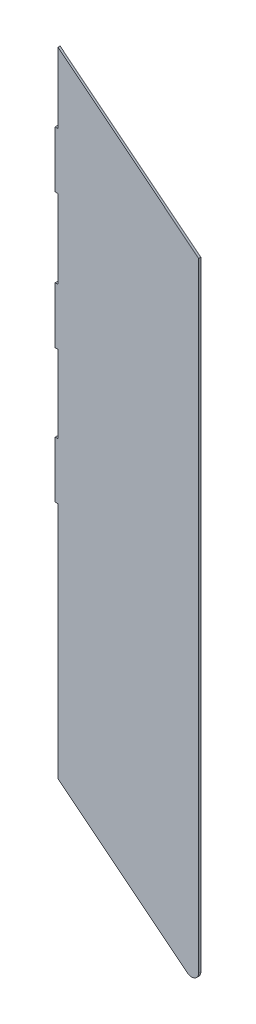
SolidWorks part; units mm, degrees
material "1345 Alloy"
ref_plane "Front Plane" through (0, 0, 0) normal (0, 0, 1) x (1, 0, 0)
ref_plane "Top Plane" through (0, 0, 0) normal (0, 1, 0) x (1, 0, 0)
ref_plane "Right Plane" through (0, 0, 0) normal (1, 0, 0) x (0, 0, -1)
sketch "Sketch1" plane through (0, 0, 0) normal (0, 0, 1) x (1, 0, 0)
  line L0 (0, -152.1368) -> (0, 297.8632)
  line L1 (0, 297.8632) -> (100, 217.8632)
  line L2 (100, 217.8632) -> (100, -232.1368)
  line L3 (0, -152.1368) -> (100, -232.1368)
  dimension "D1" = 100
  dimension "D2" = 80
extrude "Boss-Extrude1" add sketch "Sketch1" along normal blind 1.5
sketch "Sketch7" plane through (0, 0, 0) normal (-1, 0, 0) x (0, 0, 1)
  line L0 (0, 247.8632) -> (1.5, 247.8632)
  line L3 (1.5, 247.8632) -> (1.5, 207.8632)
  line L4 (1.5, 207.8632) -> (0, 207.8632)
  line L5 (0, 207.8632) -> (0, 247.8632)
  line L8 (0, 151.9834) -> (1.5, 151.9834)
  line L9 (0, 151.9834) -> (0, 111.9834)
  line L10 (0, 111.9834) -> (1.5, 111.9834)
  line L11 (1.5, 151.9834) -> (1.5, 111.9834)
  line L12 (0, 16.9834) -> (1.5, 16.9834)
  line L13 (0, 16.9834) -> (0, 56.9834)
  line L14 (0, 56.9834) -> (1.5, 56.9834)
  line L15 (1.5, 16.9834) -> (1.5, 56.9834)
  line L20 (1.5, 297.8632) -> (0, 297.8632) construction
  dimension "D1" = 40
  dimension "D2" = 50
  dimension "D3" = 40
  dimension "D4" = 40
  dimension "D6" = 55
extrude "Boss-Extrude3" add sketch "Sketch7" along normal blind 2
fillet "Fillet1" radius 5 1 edges at (100, -232.1368, 0.75)
